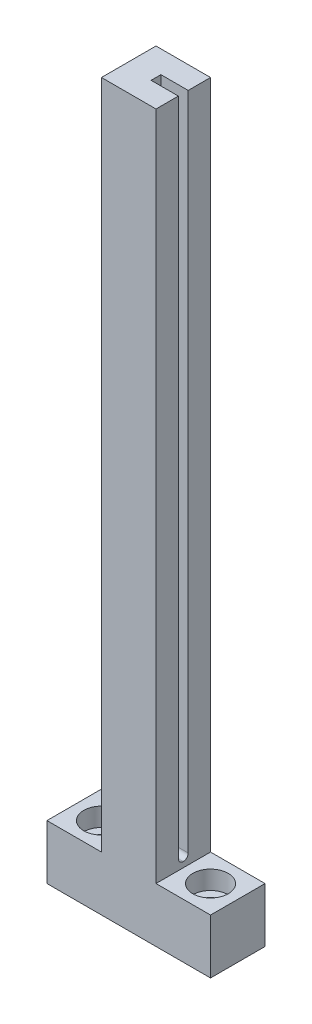
SolidWorks part; units mm, degrees
material "Polyetheretherketone (PEEK)"
ref_plane "Front Plane" through (0, 0, 0) normal (0, 0, 1) x (1, 0, 0)
ref_plane "Top Plane" through (0, 0, 0) normal (0, 1, 0) x (1, 0, 0)
ref_plane "Right Plane" through (0, 0, 0) normal (1, 0, 0) x (0, 0, -1)
sketch "Sketch1" plane through (0, 0, 0) normal (0, 1, 0) x (1, 0, 0)
  line L1 (-5, 5) -> (5, 5)
  line L2 (-5, 5) -> (-5, -5)
  line L3 (-5, -5) -> (5, -5)
  line L4 (5, 5) -> (5, -5)
  line L5 (-5, 5) -> (5, -5) construction
  line L6 (-5, -5) -> (5, 5) construction
  point P0 (0, 0)
  dimension "D1" = 10
  dimension "D2" = 10
extrude "Boss-Extrude1" add sketch "Sketch1" along normal blind 133
sketch "Sketch3" plane through (5, 0, 0) normal (1, 0, 0) x (0, 0, -1)
  line L0 (-5, 133) -> (5, 133) construction
  line L1 (-0.9, 133) -> (0.9, 133)
  line L2 (-0.9, 133) -> (-0.9, 11)
  line L3 (-0.9, 11) -> (0.9, 11)
  line L4 (0.9, 133) -> (0.9, 11)
  line L5 (0, 5.5) -> (0, -5.5) construction
  point P6 (0, 11)
  dimension "D1" = 1.8
  dimension "D2" = 122
extrude "Cut-Extrude1" cut sketch "Sketch3" against normal blind 5
fillet "Fillet1" radius 0.9 2 edges at (2.5, 11, 0.9) (2.5, 11, -0.9)
sketch "Sketch4" plane through (0, 0, 0) normal (1, 0, 0) x (0, 0, -1)
  line L0 (0, 5.5) -> (0, -5.5) construction
  line L1 (-5, 0) -> (5, 0)
  line L2 (-5, 0) -> (-5, 10)
  line L3 (-5, 10) -> (5, 10)
  line L4 (5, 0) -> (5, 10)
  line L5 (-5, 133) -> (-5, 0) construction
  line L6 (-5, 0) -> (5, 0) construction
  point P4 (0, 0)
  dimension "D1" = 10
extrude "Boss-Extrude3" add sketch "Sketch4" along normal mid plane 30
hole_wizard "CBORE for M3 Hex Socket Head Cap Screw1" positions "3DSketch1" profile "Sketch5" counterbore size "M3" standard "ISO" end condition through all
sketch3d "3DSketch1"
  line L0 (15, 10, 5) -> (5, 10, 5) construction
  point P0 (10, 10, 0)
  point P7 (10, 10, 5)
sketch "Sketch5" plane through (10, 10, 0) normal (1, 0, 0) x (0, 0, 1)
  line L0 (0, 0) -> (0, 10)
  line L1 (0, 10) -> (1.7, 10)
  line L3 (1.7, 10) -> (1.7, 3.4)
  line L4 (1.7, 3.4) -> (3.25, 3.4)
  line L5 (3.25, 3.4) -> (3.25, 0)
  line L7 (3.25, 0) -> (0, 0)
  line L11 (0, -6.35) -> (0, 107.95) construction
  dimension "Thru Hole Dia." = 3.4
  dimension "Thru Hole Depth" = 10
  dimension "C'Bore Dia." = 6.5
  dimension "C'Bore Depth" = 3.4
mirror "Mirror1" about plane through (0, 0, 0) normal (1, 0, 0) of "CBORE for M3 Hex Socket Head Cap Screw1"
hole_wizard "Ø1.0mm Dowel Hole1" positions "3DSketch2" profile "Sketch6" hole size "Ø1.0" standard "ISO"
sketch3d "3DSketch2"
  point P0 (0, 0, 0)
sketch "Sketch6" plane through (0, 0, 0) normal (1, 0, 0) x (0, 0, -1)
  line L0 (0, 0) -> (0, 8.3004)
  line L1 (0, 8.3004) -> (0.5, 8)
  line L2 (0.5, 8) -> (0.5, 0)
  line L5 (0.5, 0) -> (0, 0)
  line L10 (0, 8.3004) -> (-0.5, 8) construction
  line L11 (0, -6.35) -> (0, 107.95) construction
  dimension "Hole Dia." = 1
  dimension "Hole Depth" = 8
  dimension "Drill Angle" = 118
